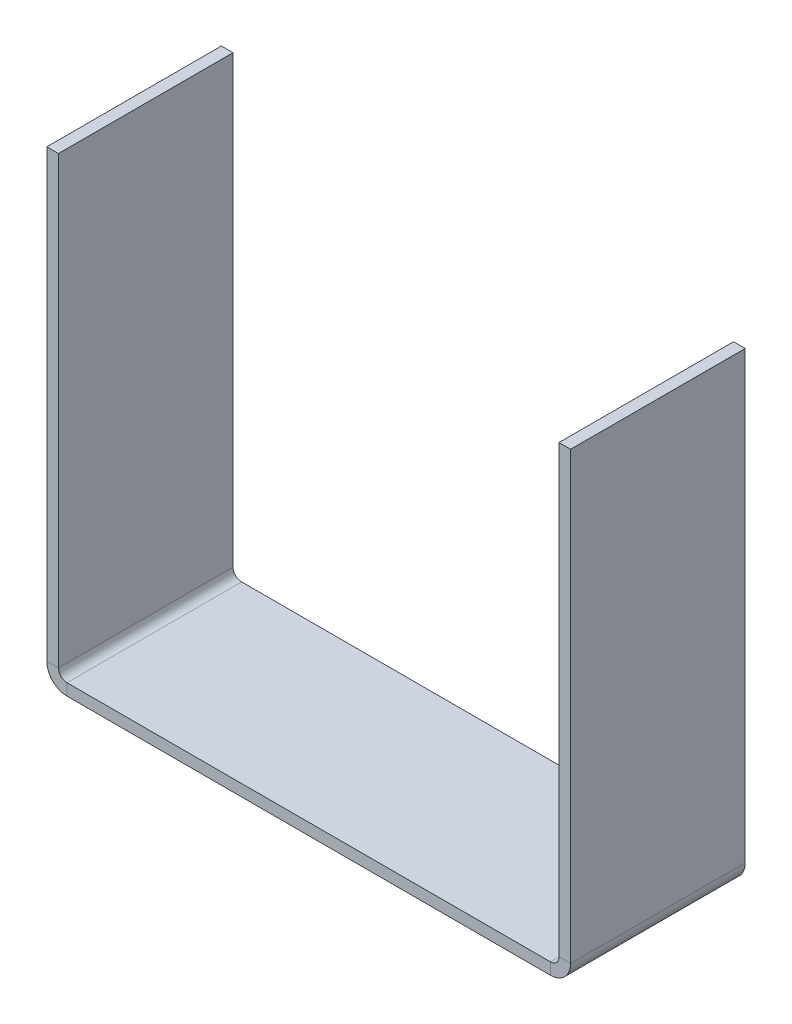
SolidWorks part; units mm, degrees
note: The reader was unsure of these and kept them because the rebuilt part matched: flange length of "Ребро-кромка1", "Ребро-кромка2".
material "Простая углеродистая сталь"
ref_plane "Спереди" through (0, 0, 0) normal (0, 0, 1) x (1, 0, 0)
ref_plane "Сверху" through (0, 0, 0) normal (0, 1, 0) x (1, 0, 0)
ref_plane "Справа" through (0, 0, 0) normal (1, 0, 0) x (0, 0, -1)
sketch "Эскиз1" plane through (0, 0, 0) normal (0, 1, 0) x (1, 0, 0)
  line L1 (0, 0) -> (45, 0)
  line L2 (0, 0) -> (0, 15)
  line L3 (0, 15) -> (45, 15)
  line L4 (45, 0) -> (45, 15)
  dimension "D1" = 45
  dimension "D2" = 15
base flange "Базовая кромка1" sketch "Эскиз1" thickness 1 reverse thickness direction no parameters "D1"=0.7366
edge flange "Ребро-кромка1" sketch "Эскиз8" flange angle 90 flange length 40 flange position material inside bend radius 0.7366 thickness 1 relief rectangular parameters "D6"=10
sketch "Эскиз8" plane through (0, 0, 0) normal (-1, 0, 0) x (0, 0, 1)
  line L0 (-15, 0) -> (0, 0) construction
  line L1 (-15, 0) -> (0, 0)
  line L2 (-15, 0) -> (-15, 39)
  line L3 (-15, 39) -> (0, 39)
  line L4 (0, 39) -> (0, 0)
bend "EdgeBend1" bend radius 0.7366 bend angle 90 parameters "D5"=1
edge flange "Ребро-кромка2" sketch "Эскиз11" flange angle 90 flange length 40 flange position material inside bend radius 0.7366 thickness 1 relief rectangular parameters "D6"=10
sketch "Эскиз11" plane through (45, 0, 0) normal (1, 0, 0) x (0, 0, -1)
  line L2 (0, 0) -> (0, 39)
  line L3 (0, 39) -> (15, 39)
  line L4 (15, 39) -> (15, 0)
  line L5 (0, 0) -> (15, 0) construction
  line L6 (0, 0) -> (15, 0)
bend "EdgeBend2" bend radius 0.7366 bend angle 90 parameters "D5"=2
sketch "Сгиб-Линии1" [suppressed] plane through (0, 0, 0) normal (0, 1, 0) x (1, 0, 0)
sketch "Граничная рамка1" [suppressed] plane through (0, 0, 0) normal (0, 1, 0) x (1, 0, 0)
sheet metal parameters "Листовой металл4" thickness 1 parameters "D1"=0.7366
flat pattern "Развертка4" [suppressed]
sketch "Сгиб-Линии2" plane through (0, 0, 0) normal (0, 1, 0) x (1, 0, 0)
sketch3d "Граничная рамка2" [suppressed]
  line L0 (150, 15, 0) -> (0, 15, 0) construction
  line L1 (150, 0, 0) -> (0, 0, 0) construction
  line L2 (150, 15, 0) -> (150, 0, 0) construction
  line L3 (0, 15, 0) -> (0, 0, 0) construction
sheet metal parameters "Листовой металл5" thickness 1 parameters "D1"=0.7366
flat pattern "Развертка4" [suppressed]
sketch "Сгиб-Линии2" plane through (0, 0, 0) normal (0, 1, 0) x (1, 0, 0)
sketch3d "Граничная рамка2" [suppressed]
  line L0 (150, 15, 0) -> (0, 15, 0) construction
  line L1 (150, 0, 0) -> (0, 0, 0) construction
  line L2 (150, 15, 0) -> (150, 0, 0) construction
  line L3 (0, 15, 0) -> (0, 0, 0) construction
bend of the flat pattern "Плоское состояние-<EdgeBend1>1"
sheet metal parameters "Листовой металл6" thickness 1 parameters "D1"=0.7366
flat pattern "Развертка4" [suppressed]
sketch "Сгиб-Линии2" plane through (0, 0, 0) normal (0, 1, 0) x (1, 0, 0)
sketch3d "Граничная рамка2" [suppressed]
  line L0 (150, 15, 0) -> (0, 15, 0) construction
  line L1 (150, 0, 0) -> (0, 0, 0) construction
  line L2 (150, 15, 0) -> (150, 0, 0) construction
  line L3 (0, 15, 0) -> (0, 0, 0) construction
bend of the flat pattern "Плоское состояние-<EdgeBend1>1"
bend of the flat pattern "Плоское состояние-<EdgeBend2>1"
